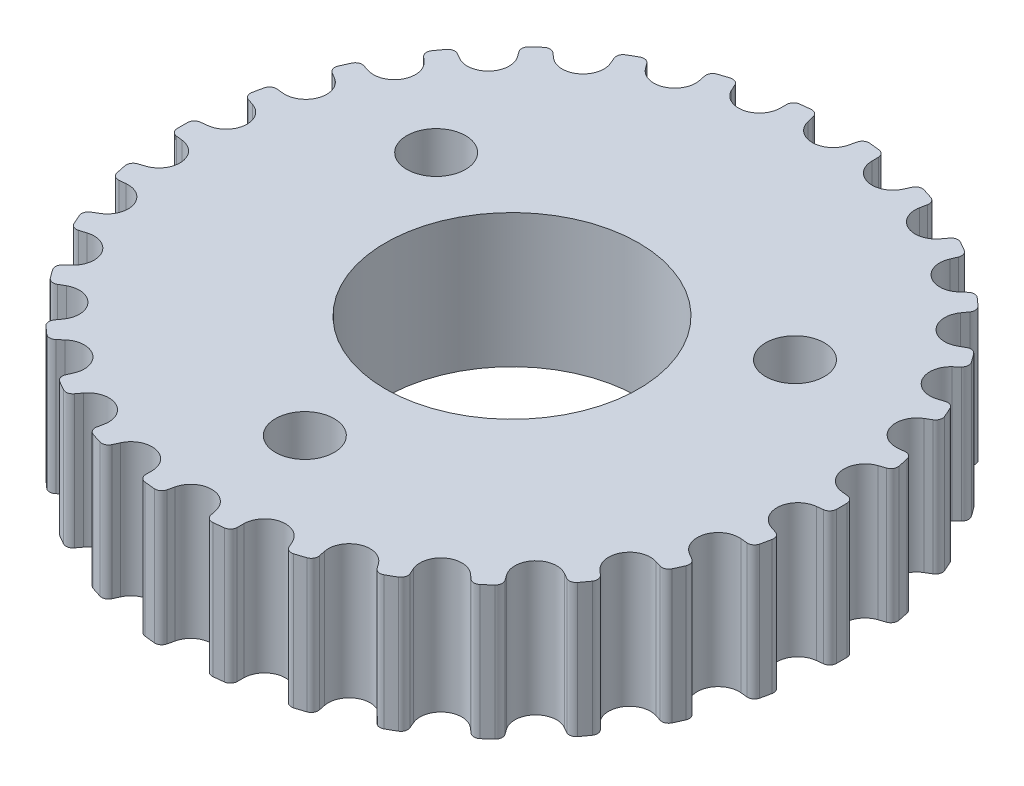
SolidWorks part; units mm, degrees
ref_plane "Front Plane" through (0, 0, 0) normal (0, 0, 1) x (1, 0, 0)
ref_plane "Top Plane" through (0, 0, 0) normal (0, 1, 0) x (1, 0, 0)
ref_plane "Right Plane" through (0, 0, 0) normal (1, 0, 0) x (0, 0, -1)
sketch "Sketch1" plane through (0, 0, 0) normal (0, 1, 0) x (1, 0, 0)
  circle A0 centre (0, 0) radius 14.3239
  dimension "D1" = 28.6479
extrude "Boss-Extrude1" add sketch "Sketch1" along normal blind 5.8
sketch "Sketch2" plane through (0, 5.8, 0) normal (0, 1, 0) x (1, 0, 0)
  line L0 (0, 0) -> (0, 14.3239) construction
  line L1 (-0.8883, 13.7564) -> (-0.95, 14.0339)
  line L2 (-2.9781, 14.0109) -> (-2.9781, 14.3239)
  line L3 (-2.9781, 14.3239) -> (2.9781, 14.3239)
  line L4 (0.8883, 13.7564) -> (0.95, 14.0339)
  line L5 (2.9781, 14.0109) -> (2.9781, 14.3239)
  circle A0 centre (0, 0) radius 14.3239 construction
  arc A1 (0.8883, 13.7564) -> (-0.8883, 13.7564) centre (0, 13.9539) cw
  arc A2 (-0.95, 14.0339) -> (-1.2694, 14.2676) centre (-1.2428, 13.9688) ccw
  arc A4 (0.95, 14.0339) -> (1.2694, 14.2676) centre (1.2428, 13.9688) cw
  arc A5 (-1.2694, 14.2676) -> (-2.9781, 14.0109) centre (0, 0) ccw
  arc A6 (1.2694, 14.2676) -> (2.9781, 14.0109) centre (0, 0) cw
  circle A8 centre (0, 0) radius 14.3239 construction
  point P11 (0, 14.3239)
  point P19 (0, 13.0439)
  dimension "D3" = 0.3
  dimension "D5" = 0.91
  dimension "D2" = 0.95
  dimension "D4" = 1.28
  dimension "D6" = 12
extrude "Cut-Extrude1" cut sketch "Sketch2" against normal through all
pattern_circular "CirPattern1" count 30 over 360 about axis through (0, 5.8, 0) along (0, -1, 0) of "Cut-Extrude1"
sketch "Sketch3" plane through (0, 0, 0) normal (0, -1, 0) x (1, 0, 0)
  circle A0 centre (0, 0) radius 5.5
  dimension "D1" = 11
extrude "Cut-Extrude2" cut sketch "Sketch3" against normal through all
sketch "Sketch4" plane through (0, 0, 0) normal (0, -1, 0) x (1, 0, 0)
  line L0 (0, 0) -> (0, 9) construction
  circle A0 centre (0, 9) radius 1.275
  circle A1 centre (7.7942, -4.5) radius 1.275
  circle A2 centre (-7.7942, -4.5) radius 1.275
  point P14 (0, 0)
  dimension "D1" = 2.55
  dimension "D2" = 9
  dimension "D3" = 3
extrude "Cut-Extrude3" cut sketch "Sketch4" against normal through all
sketch "Sketch5" plane through (0, 0, 0) normal (0, -1, 0) x (1, 0, 0)
  line L60 (8.7383, -10.682) -> (8.9513, -10.8702)
  line L61 (8.7383, -10.682) -> (8.9513, -10.8702)
  line L62 (9.875, -10.0385) -> (9.7101, -9.807)
  line L63 (9.875, -10.0385) -> (9.7101, -9.807)
  line L64 (12.5987, 6.2896) -> (12.3276, 6.2043)
  line L65 (12.5987, 6.2896) -> (12.3276, 6.2043)
  line L66 (11.5369, 7.5738) -> (11.7463, 7.766)
  line L67 (11.5369, 7.5738) -> (11.7463, 7.766)
  line L68 (-3.638, 13.3126) -> (-3.7561, 13.5712)
  line L69 (-3.638, 13.3126) -> (-3.7561, 13.5712)
  line L70 (-4.9382, 13.1871) -> (-4.8817, 12.9085)
  line L71 (-4.9382, 13.1871) -> (-4.8817, 12.9085)
  line L72 (-11.7463, 7.766) -> (-11.5369, 7.5738)
  line L73 (-11.7463, 7.766) -> (-11.5369, 7.5738)
  line L74 (-12.3276, 6.2043) -> (-12.5987, 6.2896)
  line L75 (-12.3276, 6.2043) -> (-12.5987, 6.2896)
  line L76 (-13.1043, 5.1541) -> (-12.8594, 5.0097)
  line L77 (-13.1043, 5.1541) -> (-12.8594, 5.0097)
  line L78 (-13.3481, 3.5057) -> (-13.6311, 3.5327)
  line L79 (-13.3481, 3.5057) -> (-13.6311, 3.5327)
  line L80 (-13.8895, 2.3169) -> (-13.62, 2.2266)
  line L81 (-13.8895, 2.3169) -> (-13.62, 2.2266)
  line L82 (-13.7853, 0.6538) -> (-14.0677, 0.6215)
  line L83 (-13.7853, 0.6538) -> (-14.0677, 0.6215)
  line L84 (-14.0677, -0.6215) -> (-13.7853, -0.6538)
  line L85 (-14.0677, -0.6215) -> (-13.7853, -0.6538)
  line L86 (-13.62, -2.2266) -> (-13.8895, -2.3169)
  line L87 (-13.62, -2.2266) -> (-13.8895, -2.3169)
  line L88 (-13.6311, -3.5327) -> (-13.3481, -3.5057)
  line L89 (-13.6311, -3.5327) -> (-13.3481, -3.5057)
  line L90 (-12.8594, -5.0097) -> (-13.1043, -5.1541)
  line L91 (-12.8594, -5.0097) -> (-13.1043, -5.1541)
  line L92 (-12.5987, -6.2896) -> (-12.3276, -6.2043)
  line L93 (-12.5987, -6.2896) -> (-12.3276, -6.2043)
  line L94 (-11.5369, -7.5738) -> (-11.7463, -7.766)
  line L95 (-11.5369, -7.5738) -> (-11.7463, -7.766)
  line L96 (-11.0157, -8.7716) -> (-10.7682, -8.6318)
  line L97 (-11.0157, -8.7716) -> (-10.7682, -8.6318)
  line L98 (-9.7101, -9.807) -> (-9.875, -10.0385)
  line L99 (-9.7101, -9.807) -> (-9.875, -10.0385)
  line L100 (-8.9513, -10.8702) -> (-8.7383, -10.682)
  line L101 (-8.9513, -10.8702) -> (-8.7383, -10.682)
  line L102 (-7.4589, -11.6115) -> (-7.5721, -11.8722)
  line L103 (-7.4589, -11.6115) -> (-7.5721, -11.8722)
  line L104 (-6.4956, -12.4937) -> (-6.3264, -12.2653)
  line L105 (-6.4956, -12.4937) -> (-6.3264, -12.2653)
  line L106 (-4.8817, -12.9085) -> (-4.9382, -13.1871)
  line L107 (-4.8817, -12.9085) -> (-4.9382, -13.1871)
  line L108 (-3.7561, -13.5712) -> (-3.638, -13.3126)
  line L109 (-3.7561, -13.5712) -> (-3.638, -13.3126)
  line L110 (-2.0912, -13.6414) -> (-2.0886, -13.9257)
  line L111 (-2.0912, -13.6414) -> (-2.0886, -13.9257)
  line L120 (6.3264, -12.2653) -> (6.4956, -12.4937)
  line L121 (7.5721, -11.8722) -> (7.4589, -11.6115)
  line L124 (10.7682, -8.6318) -> (11.0157, -8.7716)
  line L125 (11.7463, -7.766) -> (11.5369, -7.5738)
  line L126 (12.3276, -6.2043) -> (12.5987, -6.2896)
  line L127 (13.1043, -5.1541) -> (12.8594, -5.0097)
  line L128 (13.3481, -3.5057) -> (13.6311, -3.5327)
  line L129 (13.8895, -2.3169) -> (13.62, -2.2266)
  line L130 (13.7853, -0.6538) -> (14.0677, -0.6215)
  line L131 (14.0677, 0.6215) -> (13.7853, 0.6538)
  line L132 (13.62, 2.2266) -> (13.8895, 2.3169)
  line L133 (13.6311, 3.5327) -> (13.3481, 3.5057)
  line L134 (12.8594, 5.0097) -> (13.1043, 5.1541)
  line L137 (11.0157, 8.7716) -> (10.7682, 8.6318)
  line L138 (9.7101, 9.807) -> (9.875, 10.0385)
  line L139 (8.9513, 10.8702) -> (8.7383, 10.682)
  line L140 (7.4589, 11.6115) -> (7.5721, 11.8722)
  line L141 (6.4956, 12.4937) -> (6.3264, 12.2653)
  line L142 (4.8817, 12.9085) -> (4.9382, 13.1871)
  line L143 (3.7561, 13.5712) -> (3.638, 13.3126)
  line L144 (2.0912, 13.6414) -> (2.0886, 13.9257)
  line L145 (0.8524, 14.0556) -> (0.7907, 13.7781)
  line L146 (-0.7907, 13.7781) -> (-0.8524, 14.0556)
  line L147 (-2.0886, 13.9257) -> (-2.0912, 13.6414)
  line L150 (-6.3264, 12.2653) -> (-6.4956, 12.4937)
  line L151 (-7.5721, 11.8722) -> (-7.4589, 11.6115)
  line L152 (-8.7383, 10.682) -> (-8.9513, 10.8702)
  line L153 (-9.875, 10.0385) -> (-9.7101, 9.807)
  line L154 (-10.7682, 8.6318) -> (-11.0157, 8.7716)
  line L175 (-0.8524, -14.0556) -> (-0.7907, -13.7781)
  line L176 (0.7907, -13.7781) -> (0.8524, -14.0556)
  line L177 (2.0886, -13.9257) -> (2.0912, -13.6414)
  line L178 (3.638, -13.3126) -> (3.7561, -13.5712)
  line L179 (4.9382, -13.1871) -> (4.8817, -12.9085)
  line L180 (6.3264, -12.2653) -> (6.4956, -12.4937)
  line L181 (7.5721, -11.8722) -> (7.4589, -11.6115)
  line L184 (10.7682, -8.6318) -> (11.0157, -8.7716)
  line L185 (11.7463, -7.766) -> (11.5369, -7.5738)
  line L186 (12.3276, -6.2043) -> (12.5987, -6.2896)
  line L187 (13.1043, -5.1541) -> (12.8594, -5.0097)
  line L188 (13.3481, -3.5057) -> (13.6311, -3.5327)
  line L189 (13.8895, -2.3169) -> (13.62, -2.2266)
  line L190 (13.7853, -0.6538) -> (14.0677, -0.6215)
  line L191 (14.0677, 0.6215) -> (13.7853, 0.6538)
  line L192 (13.62, 2.2266) -> (13.8895, 2.3169)
  line L193 (13.6311, 3.5327) -> (13.3481, 3.5057)
  line L194 (12.8594, 5.0097) -> (13.1043, 5.1541)
  line L197 (11.0157, 8.7716) -> (10.7682, 8.6318)
  line L198 (9.7101, 9.807) -> (9.875, 10.0385)
  line L199 (8.9513, 10.8702) -> (8.7383, 10.682)
  line L200 (7.4589, 11.6115) -> (7.5721, 11.8722)
  line L201 (6.4956, 12.4937) -> (6.3264, 12.2653)
  line L202 (4.8817, 12.9085) -> (4.9382, 13.1871)
  line L203 (3.7561, 13.5712) -> (3.638, 13.3126)
  line L204 (2.0912, 13.6414) -> (2.0886, 13.9257)
  line L205 (0.8524, 14.0556) -> (0.7907, 13.7781)
  line L206 (-0.7907, 13.7781) -> (-0.8524, 14.0556)
  line L207 (-2.0886, 13.9257) -> (-2.0912, 13.6414)
  line L210 (-6.3264, 12.2653) -> (-6.4956, 12.4937)
  line L211 (-7.5721, 11.8722) -> (-7.4589, 11.6115)
  line L212 (-8.7383, 10.682) -> (-8.9513, 10.8702)
  line L213 (-9.875, 10.0385) -> (-9.7101, 9.807)
  line L214 (-10.7682, 8.6318) -> (-11.0157, 8.7716)
  line L235 (-0.8524, -14.0556) -> (-0.7907, -13.7781)
  line L236 (0.7907, -13.7781) -> (0.8524, -14.0556)
  line L237 (2.0886, -13.9257) -> (2.0912, -13.6414)
  line L238 (3.638, -13.3126) -> (3.7561, -13.5712)
  line L239 (4.9382, -13.1871) -> (4.8817, -12.9085)
  arc A76 (8.9513, -10.8702) -> (9.479, -10.8719) centre (9.2161, -10.5704) ccw
  arc A77 (8.9513, -10.8702) -> (9.479, -10.8719) centre (9.2161, -10.5704) ccw
  arc A78 (9.479, -10.8719) -> (9.8216, -10.5635) centre (0, 0) ccw
  arc A79 (9.479, -10.8719) -> (9.8216, -10.5635) centre (0, 0) ccw
  arc A80 (9.8216, -10.5635) -> (9.875, -10.0385) centre (9.5492, -10.2705) ccw
  arc A81 (9.8216, -10.5635) -> (9.875, -10.0385) centre (9.5492, -10.2705) ccw
  circle A120 centre (0, 0) radius 13.0439
  arc A121 (-0.8883, 13.7564) -> (0.8883, 13.7564) centre (0, 13.9539) ccw construction
  arc A128 (11.5369, 7.5738) -> (12.3276, 6.2043) centre (12.0845, 6.977) ccw
  arc A129 (11.5369, 7.5738) -> (12.3276, 6.2043) centre (12.0845, 6.977) ccw
  arc A130 (-3.7561, 13.5712) -> (-4.2375, 13.7875) centre (-4.12, 13.4051) ccw
  arc A131 (-3.7561, 13.5712) -> (-4.2375, 13.7875) centre (-4.12, 13.4051) ccw
  arc A132 (-4.2375, 13.7875) -> (-4.6759, 13.645) centre (0, 0) ccw
  arc A133 (-4.2375, 13.7875) -> (-4.6759, 13.645) centre (0, 0) ccw
  arc A134 (-4.6759, 13.645) -> (-4.9382, 13.1871) centre (-4.5462, 13.2666) ccw
  arc A135 (-4.6759, 13.645) -> (-4.9382, 13.1871) centre (-4.5462, 13.2666) ccw
  arc A136 (-11.8032, 8.2906) -> (-11.7463, 7.766) centre (-11.4759, 8.0607) ccw
  arc A137 (-11.8032, 8.2906) -> (-11.7463, 7.766) centre (-11.4759, 8.0607) ccw
  arc A138 (-12.3276, 6.2043) -> (-11.5369, 7.5738) centre (-12.0845, 6.977) ccw
  arc A139 (-12.3276, 6.2043) -> (-11.5369, 7.5738) centre (-12.0845, 6.977) ccw
  arc A140 (-12.5987, 6.2896) -> (-13.0815, 6.0766) centre (-12.7187, 5.908) ccw
  arc A141 (-12.5987, 6.2896) -> (-13.0815, 6.0766) centre (-12.7187, 5.908) ccw
  arc A142 (-13.0815, 6.0766) -> (-13.269, 5.6554) centre (0, 0) ccw
  arc A143 (-13.0815, 6.0766) -> (-13.269, 5.6554) centre (0, 0) ccw
  arc A144 (-13.269, 5.6554) -> (-13.1043, 5.1541) centre (-12.901, 5.4986) ccw
  arc A145 (-13.269, 5.6554) -> (-13.1043, 5.1541) centre (-12.901, 5.4986) ccw
  arc A146 (-13.3481, 3.5057) -> (-12.8594, 5.0097) centre (-13.271, 4.312) ccw
  arc A147 (-13.3481, 3.5057) -> (-12.8594, 5.0097) centre (-13.271, 4.312) ccw
  arc A148 (-13.6311, 3.5327) -> (-14.059, 3.224) centre (-13.6691, 3.1346) ccw
  arc A149 (-13.6311, 3.5327) -> (-14.059, 3.224) centre (-13.6691, 3.1346) ccw
  arc A150 (-14.059, 3.224) -> (-14.1549, 2.7731) centre (0, 0) ccw
  arc A151 (-14.059, 3.224) -> (-14.1549, 2.7731) centre (0, 0) ccw
  arc A152 (-14.1549, 2.7731) -> (-13.8895, 2.3169) centre (-13.7623, 2.6962) ccw
  arc A153 (-14.1549, 2.7731) -> (-13.8895, 2.3169) centre (-13.7623, 2.6962) ccw
  arc A154 (-13.7853, 0.6538) -> (-13.62, 2.2266) centre (-13.8775, 1.4586) ccw
  arc A155 (-13.7853, 0.6538) -> (-13.62, 2.2266) centre (-13.8775, 1.4586) ccw
  arc A156 (-14.0677, 0.6215) -> (-14.4221, 0.2305) centre (-14.0222, 0.2241) ccw
  arc A157 (-14.0677, 0.6215) -> (-14.4221, 0.2305) centre (-14.0222, 0.2241) ccw
  arc A158 (-14.4221, 0.2305) -> (-14.4221, -0.2305) centre (0, 0) ccw
  arc A159 (-14.4221, 0.2305) -> (-14.4221, -0.2305) centre (0, 0) ccw
  arc A160 (-14.4221, -0.2305) -> (-14.0677, -0.6215) centre (-14.0222, -0.2241) ccw
  arc A161 (-14.4221, -0.2305) -> (-14.0677, -0.6215) centre (-14.0222, -0.2241) ccw
  arc A162 (-13.62, -2.2266) -> (-13.7853, -0.6538) centre (-13.8775, -1.4586) ccw
  arc A163 (-13.62, -2.2266) -> (-13.7853, -0.6538) centre (-13.8775, -1.4586) ccw
  arc A164 (-13.8895, -2.3169) -> (-14.1549, -2.7731) centre (-13.7623, -2.6962) ccw
  arc A165 (-13.8895, -2.3169) -> (-14.1549, -2.7731) centre (-13.7623, -2.6962) ccw
  arc A166 (-14.1549, -2.7731) -> (-14.059, -3.224) centre (0, 0) ccw
  arc A167 (-14.1549, -2.7731) -> (-14.059, -3.224) centre (0, 0) ccw
  arc A168 (-14.059, -3.224) -> (-13.6311, -3.5327) centre (-13.6691, -3.1346) ccw
  arc A169 (-14.059, -3.224) -> (-13.6311, -3.5327) centre (-13.6691, -3.1346) ccw
  arc A170 (-12.8594, -5.0097) -> (-13.3481, -3.5057) centre (-13.271, -4.312) ccw
  arc A171 (-12.8594, -5.0097) -> (-13.3481, -3.5057) centre (-13.271, -4.312) ccw
  arc A172 (-13.1043, -5.1541) -> (-13.269, -5.6554) centre (-12.901, -5.4986) ccw
  arc A173 (-13.1043, -5.1541) -> (-13.269, -5.6554) centre (-12.901, -5.4986) ccw
  arc A174 (-13.269, -5.6554) -> (-13.0815, -6.0766) centre (0, 0) ccw
  arc A175 (-13.269, -5.6554) -> (-13.0815, -6.0766) centre (0, 0) ccw
  arc A176 (-13.0815, -6.0766) -> (-12.5987, -6.2896) centre (-12.7187, -5.908) ccw
  arc A177 (-13.0815, -6.0766) -> (-12.5987, -6.2896) centre (-12.7187, -5.908) ccw
  arc A178 (-11.5369, -7.5738) -> (-12.3276, -6.2043) centre (-12.0845, -6.977) ccw
  arc A179 (-11.5369, -7.5738) -> (-12.3276, -6.2043) centre (-12.0845, -6.977) ccw
  arc A180 (-11.7463, -7.766) -> (-11.8032, -8.2906) centre (-11.4759, -8.0607) ccw
  arc A181 (-11.7463, -7.766) -> (-11.8032, -8.2906) centre (-11.4759, -8.0607) ccw
  arc A182 (-11.8032, -8.2906) -> (-11.5323, -8.6636) centre (0, 0) ccw
  arc A183 (-11.8032, -8.2906) -> (-11.5323, -8.6636) centre (0, 0) ccw
  arc A184 (-11.5323, -8.6636) -> (-11.0157, -8.7716) centre (-11.2124, -8.4233) ccw
  arc A185 (-11.5323, -8.6636) -> (-11.0157, -8.7716) centre (-11.2124, -8.4233) ccw
  arc A186 (-9.7101, -9.807) -> (-10.7682, -8.6318) centre (-10.3698, -9.337) ccw
  arc A187 (-9.7101, -9.807) -> (-10.7682, -8.6318) centre (-10.3698, -9.337) ccw
  arc A188 (-9.875, -10.0385) -> (-9.8216, -10.5635) centre (-9.5492, -10.2705) ccw
  arc A189 (-9.875, -10.0385) -> (-9.8216, -10.5635) centre (-9.5492, -10.2705) ccw
  arc A190 (-9.8216, -10.5635) -> (-9.479, -10.8719) centre (0, 0) ccw
  arc A191 (-9.8216, -10.5635) -> (-9.479, -10.8719) centre (0, 0) ccw
  arc A192 (-9.479, -10.8719) -> (-8.9513, -10.8702) centre (-9.2161, -10.5704) ccw
  arc A193 (-9.479, -10.8719) -> (-8.9513, -10.8702) centre (-9.2161, -10.5704) ccw
  arc A194 (-7.4589, -11.6115) -> (-8.7383, -10.682) centre (-8.2019, -11.289) ccw
  arc A195 (-7.4589, -11.6115) -> (-8.7383, -10.682) centre (-8.2019, -11.289) ccw
  arc A196 (-7.5721, -11.8722) -> (-7.4107, -12.3747) centre (-7.2051, -12.0315) ccw
  arc A197 (-7.5721, -11.8722) -> (-7.4107, -12.3747) centre (-7.2051, -12.0315) ccw
  arc A198 (-7.4107, -12.3747) -> (-7.0114, -12.6052) centre (0, 0) ccw
  arc A199 (-7.4107, -12.3747) -> (-7.0114, -12.6052) centre (0, 0) ccw
  arc A200 (-7.0114, -12.6052) -> (-6.4956, -12.4937) centre (-6.817, -12.2556) ccw
  arc A201 (-7.0114, -12.6052) -> (-6.4956, -12.4937) centre (-6.817, -12.2556) ccw
  arc A202 (-4.8817, -12.9085) -> (-6.3264, -12.2653) centre (-5.6756, -12.7476) ccw
  arc A203 (-4.8817, -12.9085) -> (-6.3264, -12.2653) centre (-5.6756, -12.7476) ccw
  arc A204 (-4.9382, -13.1871) -> (-4.6759, -13.645) centre (-4.5462, -13.2666) ccw
  arc A205 (-4.9382, -13.1871) -> (-4.6759, -13.645) centre (-4.5462, -13.2666) ccw
  arc A206 (-4.6759, -13.645) -> (-4.2375, -13.7875) centre (0, 0) ccw
  arc A207 (-4.6759, -13.645) -> (-4.2375, -13.7875) centre (0, 0) ccw
  arc A208 (-4.2375, -13.7875) -> (-3.7561, -13.5712) centre (-4.12, -13.4051) ccw
  arc A209 (-4.2375, -13.7875) -> (-3.7561, -13.5712) centre (-4.12, -13.4051) ccw
  arc A210 (-2.0912, -13.6414) -> (-3.638, -13.3126) centre (-2.9012, -13.649) ccw
  arc A211 (-2.0912, -13.6414) -> (-3.638, -13.3126) centre (-2.9012, -13.649) ccw
  arc A212 (-2.0886, -13.9257) -> (-1.7367, -14.319) centre (-1.6886, -13.9219) ccw
  arc A213 (-2.0886, -13.9257) -> (-1.7367, -14.319) centre (-1.6886, -13.9219) ccw
  arc A214 (-1.7367, -14.319) -> (-1.2783, -14.3672) centre (0, 0) ccw
  arc A215 (-1.7367, -14.319) -> (-1.2783, -14.3672) centre (0, 0) ccw
  arc A240 (6.4956, -12.4937) -> (7.0114, -12.6052) centre (6.817, -12.2556) ccw
  arc A241 (7.0114, -12.6052) -> (7.4107, -12.3747) centre (0, 0) ccw
  arc A242 (7.4107, -12.3747) -> (7.5721, -11.8722) centre (7.2051, -12.0315) ccw
  arc A243 (8.7383, -10.682) -> (7.4589, -11.6115) centre (8.2019, -11.289) ccw
  arc A247 (10.7682, -8.6318) -> (9.7101, -9.807) centre (10.3698, -9.337) ccw
  arc A248 (11.0157, -8.7716) -> (11.5323, -8.6636) centre (11.2124, -8.4233) ccw
  arc A249 (11.5323, -8.6636) -> (11.8032, -8.2906) centre (0, 0) ccw
  arc A250 (11.8032, -8.2906) -> (11.7463, -7.766) centre (11.4759, -8.0607) ccw
  arc A251 (12.3276, -6.2043) -> (11.5369, -7.5738) centre (12.0845, -6.977) ccw
  arc A252 (12.5987, -6.2896) -> (13.0815, -6.0766) centre (12.7187, -5.908) ccw
  arc A253 (13.0815, -6.0766) -> (13.269, -5.6554) centre (0, 0) ccw
  arc A254 (13.269, -5.6554) -> (13.1043, -5.1541) centre (12.901, -5.4986) ccw
  arc A255 (13.3481, -3.5057) -> (12.8594, -5.0097) centre (13.271, -4.312) ccw
  arc A256 (13.6311, -3.5327) -> (14.059, -3.224) centre (13.6691, -3.1346) ccw
  arc A257 (14.059, -3.224) -> (14.1549, -2.7731) centre (0, 0) ccw
  arc A258 (14.1549, -2.7731) -> (13.8895, -2.3169) centre (13.7623, -2.6962) ccw
  arc A259 (13.7853, -0.6538) -> (13.62, -2.2266) centre (13.8775, -1.4586) ccw
  arc A260 (14.0677, -0.6215) -> (14.4221, -0.2305) centre (14.0222, -0.2241) ccw
  arc A261 (14.4221, -0.2305) -> (14.4221, 0.2305) centre (0, 0) ccw
  arc A262 (14.4221, 0.2305) -> (14.0677, 0.6215) centre (14.0222, 0.2241) ccw
  arc A263 (13.62, 2.2266) -> (13.7853, 0.6538) centre (13.8775, 1.4586) ccw
  arc A264 (13.8895, 2.3169) -> (14.1549, 2.7731) centre (13.7623, 2.6962) ccw
  arc A265 (14.1549, 2.7731) -> (14.059, 3.224) centre (0, 0) ccw
  arc A266 (14.059, 3.224) -> (13.6311, 3.5327) centre (13.6691, 3.1346) ccw
  arc A267 (12.8594, 5.0097) -> (13.3481, 3.5057) centre (13.271, 4.312) ccw
  arc A268 (13.1043, 5.1541) -> (13.269, 5.6554) centre (12.901, 5.4986) ccw
  arc A269 (13.269, 5.6554) -> (13.0815, 6.0766) centre (0, 0) ccw
  arc A270 (13.0815, 6.0766) -> (12.5987, 6.2896) centre (12.7187, 5.908) ccw
  arc A272 (11.7463, 7.766) -> (11.8032, 8.2906) centre (11.4759, 8.0607) ccw
  arc A273 (11.8032, 8.2906) -> (11.5323, 8.6636) centre (0, 0) ccw
  arc A274 (11.5323, 8.6636) -> (11.0157, 8.7716) centre (11.2124, 8.4233) ccw
  arc A275 (9.7101, 9.807) -> (10.7682, 8.6318) centre (10.3698, 9.337) ccw
  arc A276 (9.875, 10.0385) -> (9.8216, 10.5635) centre (9.5492, 10.2705) ccw
  arc A277 (9.8216, 10.5635) -> (9.479, 10.8719) centre (0, 0) ccw
  arc A278 (9.479, 10.8719) -> (8.9513, 10.8702) centre (9.2161, 10.5704) ccw
  arc A279 (7.4589, 11.6115) -> (8.7383, 10.682) centre (8.2019, 11.289) ccw
  arc A280 (7.5721, 11.8722) -> (7.4107, 12.3747) centre (7.2051, 12.0315) ccw
  arc A281 (7.4107, 12.3747) -> (7.0114, 12.6052) centre (0, 0) ccw
  arc A282 (7.0114, 12.6052) -> (6.4956, 12.4937) centre (6.817, 12.2556) ccw
  arc A283 (4.8817, 12.9085) -> (6.3264, 12.2653) centre (5.6756, 12.7476) ccw
  arc A284 (4.9382, 13.1871) -> (4.6759, 13.645) centre (4.5462, 13.2666) ccw
  arc A285 (4.6759, 13.645) -> (4.2375, 13.7875) centre (0, 0) ccw
  arc A286 (4.2375, 13.7875) -> (3.7561, 13.5712) centre (4.12, 13.4051) ccw
  arc A287 (2.0912, 13.6414) -> (3.638, 13.3126) centre (2.9012, 13.649) ccw
  arc A288 (2.0886, 13.9257) -> (1.7367, 14.319) centre (1.6886, 13.9219) ccw
  arc A289 (1.7367, 14.319) -> (1.2783, 14.3672) centre (0, 0) ccw
  arc A290 (1.2783, 14.3672) -> (0.8524, 14.0556) centre (1.2428, 13.9688) ccw
  arc A291 (-0.7907, 13.7781) -> (0.7907, 13.7781) centre (0, 13.9539) ccw
  arc A292 (-0.8524, 14.0556) -> (-1.2783, 14.3672) centre (-1.2428, 13.9688) ccw
  arc A293 (-1.2783, 14.3672) -> (-1.7367, 14.319) centre (0, 0) ccw
  arc A294 (-1.7367, 14.319) -> (-2.0886, 13.9257) centre (-1.6886, 13.9219) ccw
  arc A295 (-3.638, 13.3126) -> (-2.0912, 13.6414) centre (-2.9012, 13.649) ccw
  arc A299 (-6.3264, 12.2653) -> (-4.8817, 12.9085) centre (-5.6756, 12.7476) ccw
  arc A300 (-6.4956, 12.4937) -> (-7.0114, 12.6052) centre (-6.817, 12.2556) ccw
  arc A301 (-7.0114, 12.6052) -> (-7.4107, 12.3747) centre (0, 0) ccw
  arc A302 (-7.4107, 12.3747) -> (-7.5721, 11.8722) centre (-7.2051, 12.0315) ccw
  arc A303 (-8.7383, 10.682) -> (-7.4589, 11.6115) centre (-8.2019, 11.289) ccw
  arc A304 (-8.9513, 10.8702) -> (-9.479, 10.8719) centre (-9.2161, 10.5704) ccw
  arc A305 (-9.479, 10.8719) -> (-9.8216, 10.5635) centre (0, 0) ccw
  arc A306 (-9.8216, 10.5635) -> (-9.875, 10.0385) centre (-9.5492, 10.2705) ccw
  arc A307 (-10.7682, 8.6318) -> (-9.7101, 9.807) centre (-10.3698, 9.337) ccw
  arc A308 (-11.0157, 8.7716) -> (-11.5323, 8.6636) centre (-11.2124, 8.4233) ccw
  arc A309 (-11.5323, 8.6636) -> (-11.8032, 8.2906) centre (0, 0) ccw
  arc A350 (-1.2783, -14.3672) -> (-0.8524, -14.0556) centre (-1.2428, -13.9688) ccw
  arc A351 (0.7907, -13.7781) -> (-0.7907, -13.7781) centre (0, -13.9539) ccw
  arc A352 (0.8524, -14.0556) -> (1.2783, -14.3672) centre (1.2428, -13.9688) ccw
  arc A353 (1.2783, -14.3672) -> (1.7367, -14.319) centre (0, 0) ccw
  arc A354 (1.7367, -14.319) -> (2.0886, -13.9257) centre (1.6886, -13.9219) ccw
  arc A355 (3.638, -13.3126) -> (2.0912, -13.6414) centre (2.9012, -13.649) ccw
  arc A356 (3.7561, -13.5712) -> (4.2375, -13.7875) centre (4.12, -13.4051) ccw
  arc A357 (4.2375, -13.7875) -> (4.6759, -13.645) centre (0, 0) ccw
  arc A358 (4.6759, -13.645) -> (4.9382, -13.1871) centre (4.5462, -13.2666) ccw
  arc A359 (6.3264, -12.2653) -> (4.8817, -12.9085) centre (5.6756, -12.7476) ccw
  arc A360 (6.4956, -12.4937) -> (7.0114, -12.6052) centre (6.817, -12.2556) ccw
  arc A361 (7.0114, -12.6052) -> (7.4107, -12.3747) centre (0, 0) ccw
  arc A362 (7.4107, -12.3747) -> (7.5721, -11.8722) centre (7.2051, -12.0315) ccw
  arc A363 (8.7383, -10.682) -> (7.4589, -11.6115) centre (8.2019, -11.289) ccw
  arc A367 (10.7682, -8.6318) -> (9.7101, -9.807) centre (10.3698, -9.337) ccw
  arc A368 (11.0157, -8.7716) -> (11.5323, -8.6636) centre (11.2124, -8.4233) ccw
  arc A369 (11.5323, -8.6636) -> (11.8032, -8.2906) centre (0, 0) ccw
  arc A370 (11.8032, -8.2906) -> (11.7463, -7.766) centre (11.4759, -8.0607) ccw
  arc A371 (12.3276, -6.2043) -> (11.5369, -7.5738) centre (12.0845, -6.977) ccw
  arc A372 (12.5987, -6.2896) -> (13.0815, -6.0766) centre (12.7187, -5.908) ccw
  arc A373 (13.0815, -6.0766) -> (13.269, -5.6554) centre (0, 0) ccw
  arc A374 (13.269, -5.6554) -> (13.1043, -5.1541) centre (12.901, -5.4986) ccw
  arc A375 (13.3481, -3.5057) -> (12.8594, -5.0097) centre (13.271, -4.312) ccw
  arc A376 (13.6311, -3.5327) -> (14.059, -3.224) centre (13.6691, -3.1346) ccw
  arc A377 (14.059, -3.224) -> (14.1549, -2.7731) centre (0, 0) ccw
  arc A378 (14.1549, -2.7731) -> (13.8895, -2.3169) centre (13.7623, -2.6962) ccw
  arc A379 (13.7853, -0.6538) -> (13.62, -2.2266) centre (13.8775, -1.4586) ccw
  arc A380 (14.0677, -0.6215) -> (14.4221, -0.2305) centre (14.0222, -0.2241) ccw
  arc A381 (14.4221, -0.2305) -> (14.4221, 0.2305) centre (0, 0) ccw
  arc A382 (14.4221, 0.2305) -> (14.0677, 0.6215) centre (14.0222, 0.2241) ccw
  arc A383 (13.62, 2.2266) -> (13.7853, 0.6538) centre (13.8775, 1.4586) ccw
  arc A384 (13.8895, 2.3169) -> (14.1549, 2.7731) centre (13.7623, 2.6962) ccw
  arc A385 (14.1549, 2.7731) -> (14.059, 3.224) centre (0, 0) ccw
  arc A386 (14.059, 3.224) -> (13.6311, 3.5327) centre (13.6691, 3.1346) ccw
  arc A387 (12.8594, 5.0097) -> (13.3481, 3.5057) centre (13.271, 4.312) ccw
  arc A388 (13.1043, 5.1541) -> (13.269, 5.6554) centre (12.901, 5.4986) ccw
  arc A389 (13.269, 5.6554) -> (13.0815, 6.0766) centre (0, 0) ccw
  arc A390 (13.0815, 6.0766) -> (12.5987, 6.2896) centre (12.7187, 5.908) ccw
  arc A392 (11.7463, 7.766) -> (11.8032, 8.2906) centre (11.4759, 8.0607) ccw
  arc A393 (11.8032, 8.2906) -> (11.5323, 8.6636) centre (0, 0) ccw
  arc A394 (11.5323, 8.6636) -> (11.0157, 8.7716) centre (11.2124, 8.4233) ccw
  arc A395 (9.7101, 9.807) -> (10.7682, 8.6318) centre (10.3698, 9.337) ccw
  arc A396 (9.875, 10.0385) -> (9.8216, 10.5635) centre (9.5492, 10.2705) ccw
  arc A397 (9.8216, 10.5635) -> (9.479, 10.8719) centre (0, 0) ccw
  arc A398 (9.479, 10.8719) -> (8.9513, 10.8702) centre (9.2161, 10.5704) ccw
  arc A399 (7.4589, 11.6115) -> (8.7383, 10.682) centre (8.2019, 11.289) ccw
  arc A400 (7.5721, 11.8722) -> (7.4107, 12.3747) centre (7.2051, 12.0315) ccw
  arc A401 (7.4107, 12.3747) -> (7.0114, 12.6052) centre (0, 0) ccw
  arc A402 (7.0114, 12.6052) -> (6.4956, 12.4937) centre (6.817, 12.2556) ccw
  arc A403 (4.8817, 12.9085) -> (6.3264, 12.2653) centre (5.6756, 12.7476) ccw
  arc A404 (4.9382, 13.1871) -> (4.6759, 13.645) centre (4.5462, 13.2666) ccw
  arc A405 (4.6759, 13.645) -> (4.2375, 13.7875) centre (0, 0) ccw
  arc A406 (4.2375, 13.7875) -> (3.7561, 13.5712) centre (4.12, 13.4051) ccw
  arc A407 (2.0912, 13.6414) -> (3.638, 13.3126) centre (2.9012, 13.649) ccw
  arc A408 (2.0886, 13.9257) -> (1.7367, 14.319) centre (1.6886, 13.9219) ccw
  arc A409 (1.7367, 14.319) -> (1.2783, 14.3672) centre (0, 0) ccw
  arc A410 (1.2783, 14.3672) -> (0.8524, 14.0556) centre (1.2428, 13.9688) ccw
  arc A411 (-0.7907, 13.7781) -> (0.7907, 13.7781) centre (0, 13.9539) ccw
  arc A412 (-0.8524, 14.0556) -> (-1.2783, 14.3672) centre (-1.2428, 13.9688) ccw
  arc A413 (-1.2783, 14.3672) -> (-1.7367, 14.319) centre (0, 0) ccw
  arc A414 (-1.7367, 14.319) -> (-2.0886, 13.9257) centre (-1.6886, 13.9219) ccw
  arc A415 (-3.638, 13.3126) -> (-2.0912, 13.6414) centre (-2.9012, 13.649) ccw
  arc A419 (-6.3264, 12.2653) -> (-4.8817, 12.9085) centre (-5.6756, 12.7476) ccw
  arc A420 (-6.4956, 12.4937) -> (-7.0114, 12.6052) centre (-6.817, 12.2556) ccw
  arc A421 (-7.0114, 12.6052) -> (-7.4107, 12.3747) centre (0, 0) ccw
  arc A422 (-7.4107, 12.3747) -> (-7.5721, 11.8722) centre (-7.2051, 12.0315) ccw
  arc A423 (-8.7383, 10.682) -> (-7.4589, 11.6115) centre (-8.2019, 11.289) ccw
  arc A424 (-8.9513, 10.8702) -> (-9.479, 10.8719) centre (-9.2161, 10.5704) ccw
  arc A425 (-9.479, 10.8719) -> (-9.8216, 10.5635) centre (0, 0) ccw
  arc A426 (-9.8216, 10.5635) -> (-9.875, 10.0385) centre (-9.5492, 10.2705) ccw
  arc A427 (-10.7682, 8.6318) -> (-9.7101, 9.807) centre (-10.3698, 9.337) ccw
  arc A428 (-11.0157, 8.7716) -> (-11.5323, 8.6636) centre (-11.2124, 8.4233) ccw
  arc A429 (-11.5323, 8.6636) -> (-11.8032, 8.2906) centre (0, 0) ccw
  arc A470 (-1.2783, -14.3672) -> (-0.8524, -14.0556) centre (-1.2428, -13.9688) ccw
  arc A471 (0.7907, -13.7781) -> (-0.7907, -13.7781) centre (0, -13.9539) ccw
  arc A472 (0.8524, -14.0556) -> (1.2783, -14.3672) centre (1.2428, -13.9688) ccw
  arc A473 (1.2783, -14.3672) -> (1.7367, -14.319) centre (0, 0) ccw
  arc A474 (1.7367, -14.319) -> (2.0886, -13.9257) centre (1.6886, -13.9219) ccw
  arc A475 (3.638, -13.3126) -> (2.0912, -13.6414) centre (2.9012, -13.649) ccw
  arc A476 (3.7561, -13.5712) -> (4.2375, -13.7875) centre (4.12, -13.4051) ccw
  arc A477 (4.2375, -13.7875) -> (4.6759, -13.645) centre (0, 0) ccw
  arc A478 (4.6759, -13.645) -> (4.9382, -13.1871) centre (4.5462, -13.2666) ccw
  arc A479 (6.3264, -12.2653) -> (4.8817, -12.9085) centre (5.6756, -12.7476) ccw
  dimension "D1" = 0.1
extrude "Boss-Extrude2" [suppressed] add sketch "Sketch5" against normal up to surface (5.8 mm away) up to face at (7.7942, 5.8, -5.775)
equation "\"smallPulleyTeeth\"= 15"
equation "\"largePulleyTeeth\"= 30"
equation "\"eighthThick\"= 2.9mm"
equation "\"D1@Sketch1\"=3*\"largePulleyTeeth\"/pi"
equation "\"D1@Boss-Extrude1\" = \"eighthThick\" * 2"
equation "\"D6@Sketch2\"=360/\"largePulleyTeeth\""
equation "\"quarterThick\"=5.9mm"
equation "\"D1@CirPattern1\"=\"largePulleyTeeth\""
equation "\"sixteenthThick\" = 1.7mm"
equation "\"OD\" = 145mm"
equation "\"puckAngle\" = 60.5deg"
equation "\"puckDiam\" = 76.5mm"
equation "\"axlePress\" = 5.9mm"
equation "\"press\" = 0.2mm"
equation "\"wheelClear\" = 0.3mm"
equation "\"10-32clear\" = 4.5mm"
equation "\"D1@Sketch4\"=\"4-40clear\""
equation "\"6-32clear\" = 3.3mm"
equation "\"8-32clear\" = 4.0mm"
equation "\"4-40clear\" = 2.55mm"
equation "\"wheelHeight\" = 22mm"
equation "\"wheelWell\" = 65mm"
